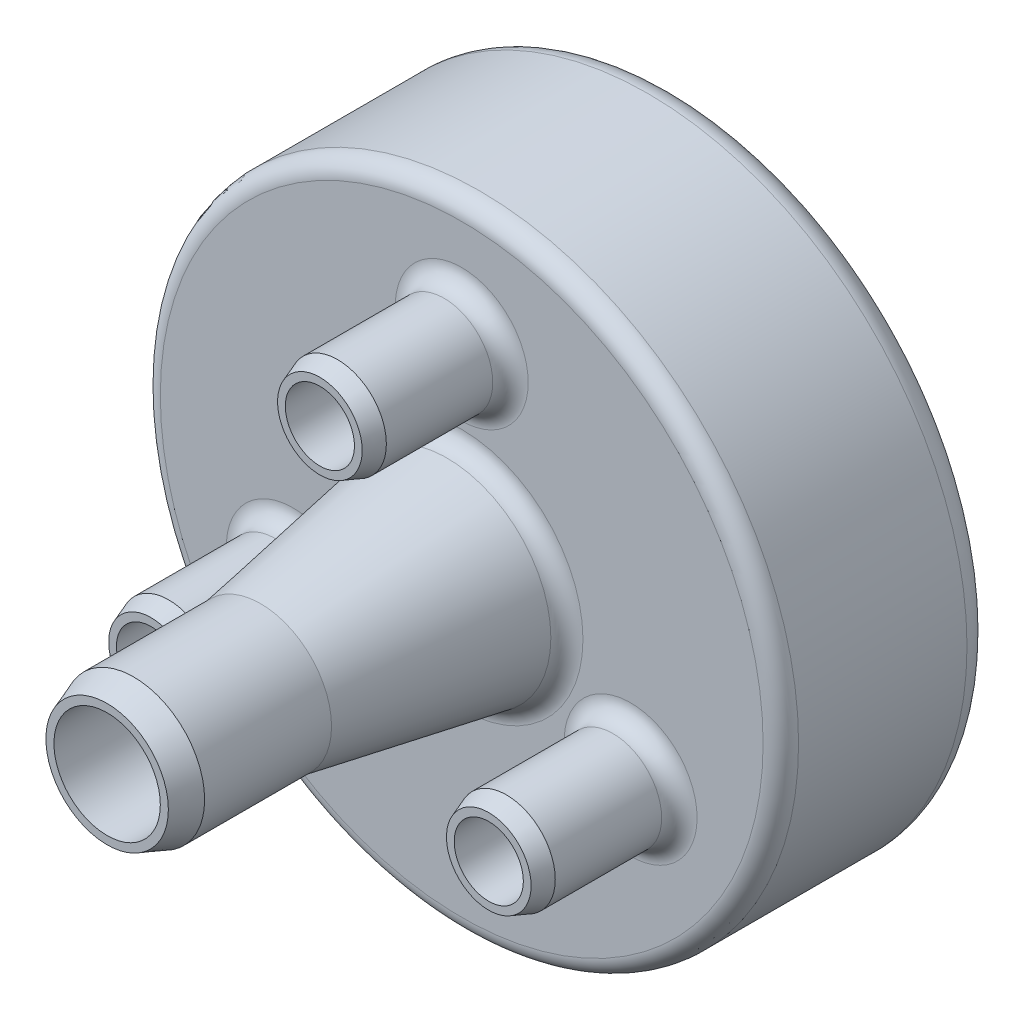
SolidWorks part; units mm, degrees
ref_plane "Front Plane" through (0, 0, 0) normal (0, 0, 1) x (1, 0, 0)
ref_plane "Top Plane" through (0, 0, 0) normal (0, 1, 0) x (1, 0, 0)
ref_plane "Right Plane" through (0, 0, 0) normal (1, 0, 0) x (0, 0, -1)
sketch "Sketch1" plane through (0, 0, 0) normal (0, 0, 1) x (1, 0, 0)
  circle A0 centre (0, 0) radius 18
  circle A1 centre (0, 0) radius 15
  circle A2 centre (0, 0) radius 4
  circle A3 centre (0, 11) radius 2.75
  circle A4 centre (0, 11) radius 1.95
  circle A5 centre (0, 0) radius 3
  dimension "D1" = 30
  dimension "D2" = 8
  dimension "D3" = 5.5
  dimension "D5" = 3
  dimension "D4" = 11
  dimension "D6" = 0.8
  dimension "D7" = 1
extrude "Boss-Extrude1" add sketch "Sketch1" against normal blind 10 contours A0 A1 region at (-17.4909, 0, 0)
extrude "Boss-Extrude2" add sketch "Sketch1<3>" against normal blind 2 contours A4 | A3 A4 | A1 A3 A2 | A2 A5 | A0 A1 region at (-17.4909, 0, 0) region at (-14.5757, 0, 0) region at (-3.8869, 0, 0) region at (-2.6722, 11, 0) region at (0, 11, 0)
sketch "Sketch1<3>" plane through (0, 0, 0) normal (0, 0, 1) x (1, 0, 0) same geometry as "Sketch1"
extrude "Boss-Extrude3" add sketch "Sketch1<4>" along normal blind 8 contours A3 A4 region at (-2.6722, 11, 0)
sketch "Sketch1<4>" plane through (0, 0, 0) normal (0, 0, 1) x (1, 0, 0) same geometry as "Sketch1"
extrude "Boss-Extrude4" add sketch "Sketch1<5>" along normal blind 20 contours A2 A5 region at (-3.8869, 0, 0)
sketch "Sketch1<5>" plane through (0, 0, 0) normal (0, 0, 1) x (1, 0, 0) same geometry as "Sketch1"
sketch "Sketch2" plane through (0, 0, -10) normal (0, 0, -1) x (-1, 0, 0)
  circle A1 centre (0, 0) radius 18
  circle A2 centre (0, 0) radius 18
  dimension "D1" = 0
extrude "Boss-Extrude5" add sketch "Sketch2" along normal blind 2
sketch "Sketch3" plane through (0, 0, 8) normal (0, 0, 1) x (1, 0, 0)
  circle A0 centre (0, 11) radius 1.95 construction
  circle A3 centre (0, 11) radius 1.95
extrude "Cut-Extrude1" cut sketch "Sketch3" against normal up to surface (18 mm away) contours A3 up to face at (15, 0, -10)
fillet "Fillet2" radius 1.5 1 edges at (3, 0, -2)
fillet "Fillet3" radius 1.5 1 edges at (1.95, 11, -2)
pattern_circular "CirPattern2" count 3 over 360 about axis through (0, 0, 20) along (0, 0, -1) of "Fillet3", "Boss-Extrude3", "Cut-Extrude1" reverse direction yes
chamfer "Chamfer1" distance 2 angle 80 1 edges at (4, 0, 0) first distance on face at (8.1513, -7.8816, 0)
fillet "Fillet4" radius 1 5 edges at (18, 0, 0) (2.75, 11, 0) (-10.9013, -3.1184, 0) (8.1513, -7.8816, 0) (6, 0, 0)
chamfer "Chamfer2" distance 1 angle 20 3 edges at (-10.9013, -3.1184, 8) (8.1513, -7.8816, 8) (2.75, 11, 8) first distance on face at (-6.7763, -5.5, 1) first distance on face at (12.2763, -5.5, 1) first distance on face at (2.75, 11, 1)
chamfer "Chamfer3" distance 1.5 angle 20 1 edges at (4, 0, 20) first distance on face at (4, 0, 11.3426)
fillet "Fillet5" radius 1.5 1 edges at (-18, 0, -12)
